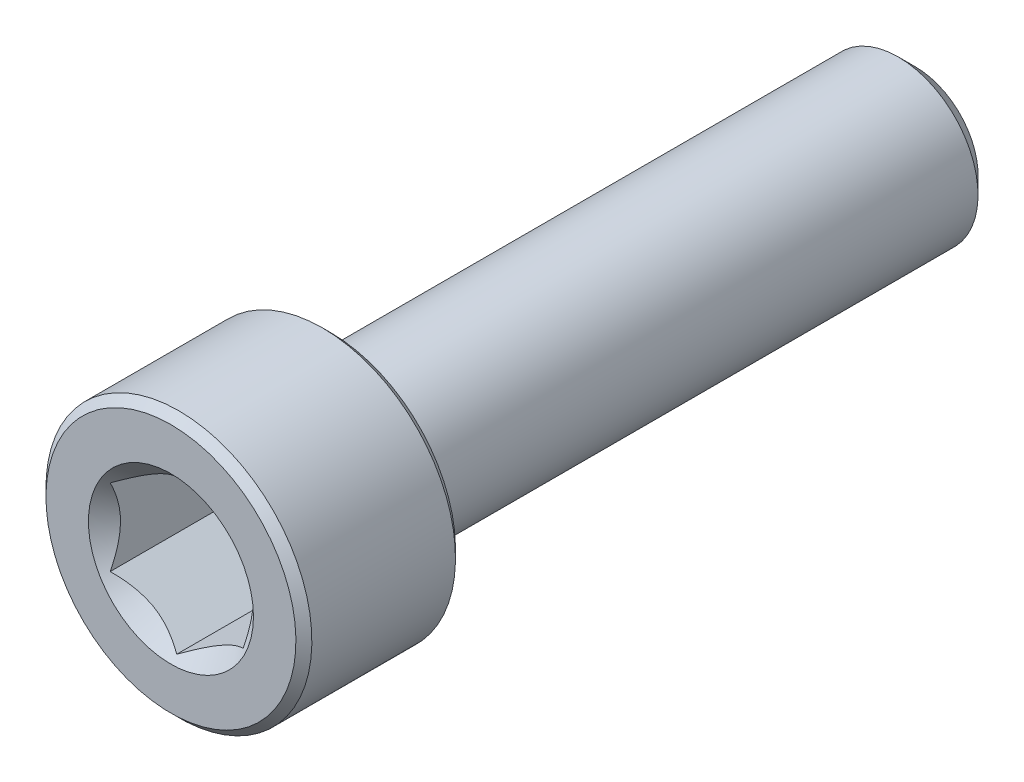
SolidWorks part; units mm, degrees
ref_plane "Front Plane" through (0, 0, 0) normal (0, 0, 1) x (1, 0, 0)
ref_plane "Top Plane" through (0, 0, 0) normal (0, 1, 0) x (1, 0, 0)
ref_plane "Right Plane" through (0, 0, 0) normal (1, 0, 0) x (0, 0, -1)
sketch "Sketch1" plane through (0, 0, 0) normal (1, 0, 0) x (0, 0, -1)
  line L0 (-14, 0) -> (14, 0) construction
  line L1 (14, 0) -> (14, 2.3505) construction
  line L2 (14, 2.3505) -> (13.3505, 3) construction
  line L3 (13.3505, 3) -> (13.25, 3) construction
  line L4 (13.25, 3) -> (-8, 3) construction
  line L5 (-8, 3) -> (-8, 5) construction
  line L6 (-8, 5) -> (-14, 5) construction
  line L7 (-14, 5) -> (-14, 0) construction
  line L8 (14, 2.3505) -> (14, 3) construction
  line L9 (13.9375, 3.1083) -> (14.4375, 2.2422) construction
  line L10 (14.4375, 2.2422) -> (14.9375, 3.1083) construction
  line L11 (14.9375, 3.1083) -> (13.9375, 3.1083) construction
  line L12 (14.4375, 3.1083) -> (14.4375, 3) construction
  line L13 (14.4375, 2.2422) -> (14.4375, 2.3505) construction
  line L14 (14.375, 2.3505) -> (14.5, 2.3505) construction
  line L15 (14, 3) -> (14.875, 3) construction
  line L16 (13.9688, 3.0541) -> (14.9062, 3.0541) construction
  line L17 (14, 0) -> (14, -3) construction
  line L18 (-8.3, 5) -> (-8, 4.7) construction
  line L19 (-13.7, 5) -> (-14, 4.7) construction
  line L20 (-8, 3) -> (-8, 0) construction
  line L21 (-8, 1.5) -> (-0.6667, 1.5) construction
  line L22 (-0.6667, 1.5) -> (6.6667, 1.5) construction
  line L23 (6.6667, 1.5) -> (14, 1.5) construction
  line L24 (-0.6667, 1.5) -> (-0.6667, 3) construction
  line L25 (-0.6667, 3) -> (-0.6667, 5) construction
  line L26 (6.6667, 1.5) -> (6.6667, 5) construction
  point P0 (-14, 2.5)
  point P3 (11.5, 3)
  point P4 (0, 0)
  point P18 (6.6667, 3)
  point P22 (14.4375, 2.3505)
  point P24 (13.25, 3)
  point P25 (14.4375, 3)
  point P28 (14.4375, 3.0541)
  point P29 (11.5, -3)
  point P30 (-0.6667, 3)
  point P31 (-11, 5)
  point P37 (-9.05, 5)
  point P38 (-13.55, 5)
  point P45 (-0.6667, 1.5)
  point P46 (6.6667, 1.5)
  dimension "D2" = 0.125
  dimension "D7" = 0.3
  dimension "D8" = 0.3
  dimension "D9" = 0.3
  dimension "D10" = 0.15
  dimension "D11" = 0.75
  dimension "Drive Size" = 5
  dimension "Head Diameter" = 10
  dimension "Head Height" = 6
  dimension "Thread Pitch" = 1
  dimension "Thread Dia" = 6
  dimension "Length" = 22
  dimension "D12" = 0.75
  dimension "D4" = 2.5
  dimension "D3" = 45
sketch "Sketch2" plane through (0, 0, 0) normal (1, 0, 0) x (0, 0, -1)
  line L0 (-14, 0) -> (-14, 4.7)
  line L1 (-13.7, 5) -> (-8.3, 5)
  line L2 (-8, 4.7) -> (-8, 3.3)
  line L4 (13.3505, 3) -> (14, 2.3505)
  line L5 (14, 2.3505) -> (14, 0)
  line L6 (-8, 5) -> (-14, 5) construction
  line L7 (14, 0) -> (-14, 0)
  line L8 (-13.7, 5) -> (-14, 4.7) construction
  line L10 (-13.7, 5) -> (-14, 4.7)
  line L14 (-8.3, 5) -> (-8, 4.7) construction
  line L16 (-8.3, 5) -> (-8, 4.7)
  line L17 (-8, 3) -> (-8, 5) construction
  line L19 (-7.7, 3) -> (13.3505, 3)
  line L20 (13.25, 3) -> (-8, 3) construction
  arc A1 (-8, 3.3) -> (-7.7, 3) centre (-7.7, 3.3) ccw
  dimension "D3" = 0.3
revolve "Revolve1" add sketch "Sketch2" angle 360 about L7
sketch "Sketch3" plane through (0, 0, 14) normal (0, 0, 1) x (1, 0, 0)
  line L1 (2.5, -1.4434) -> (2.5, 1.4434)
  line L2 (2.5, 1.4434) -> (0, 2.8868)
  line L3 (0, 2.8868) -> (-2.5, 1.4434)
  line L4 (-2.5, 1.4434) -> (-2.5, -1.4434)
  line L5 (-2.5, -1.4434) -> (0, -2.8868)
  line L6 (0, -2.8868) -> (2.5, -1.4434)
  circle A0 centre (0, 0) radius 2.5 construction
  circle A1 centre (0, 0) radius 5 construction
  circle A2 centre (0, 0) radius 5 construction
  circle A3 centre (0, 0) radius 2.8868 construction
  point P13 (0, 0)
  dimension "D1" = 5.7735
extrude "Cut-Extrude1" cut sketch "Sketch3" against normal offset from surface (5 mm away) 1 up to face at (0, 4.7, 8)
sketch "Sketch4" plane through (0, 0, 14) normal (0, 0, 1) x (1, 0, 0)
  circle A0 centre (0, 0) radius 3.1033
  dimension "D1" = 6.2065
extrude "Cut-Extrude2" cut sketch "Sketch4" against normal up to vertex (3 mm away) draft 45 up to point (0, 5, 11)
sketch "Sketch11" plane through (0, 0, 0) normal (1, 0, 0) x (0, 0, -1)
  line L0 (-14, 0) -> (14, 0) construction
  line L1 (-14, 0) -> (14, 0) construction
  line L2 (-3.875, 0) -> (-3.875, 3) construction
  line L3 (13.25, 3) -> (-8, 3) construction
  line L4 (9.875, 0) -> (9.875, 3) construction
  line L6 (14, 2.3505) -> (14, 3) construction
  point P2 (-3.875, 0)
  point P3 (9.875, 0)
  dimension "D1" = 4.125
  dimension "D2" = 4.125
sketch "Sketch6" [suppressed] plane through (0, 0, -14) normal (0, 0, -1) x (-1, 0, 0)
  circle A0 centre (0, 0) radius 3
curve "Helix/Spiral1" [suppressed] pitch 1 height 23 turns 23
sketch "Sketch10" [suppressed] plane through (0, 0, 0) normal (1, 0, 0) x (0, 0, -1)
  line L0 (-7.7, -5) -> (-7.7, 5)
  line L5 (-14, 0) -> (14, 0) construction
  line L6 (-7.7, 3) -> (-7.7, -3) construction
  point P3 (-7.7, 0)
split "Split1" [suppressed] bodies to split 106
sketch "Sketch7" [suppressed] plane through (0, 0, 0) normal (1, 0, 0) x (0, 0, -1)
  line L0 (13.9688, 3.0541) -> (14.9062, 3.0541)
  line L1 (14.9062, 3.0541) -> (14.5, 2.3505)
  line L2 (14.5, 2.3505) -> (14.375, 2.3505)
  line L3 (14.375, 2.3505) -> (13.9688, 3.0541)
sweep "Cut-Sweep1" [suppressed] cut profiles "Sketch7" path "Helix/Spiral1"
sketch "Sketch8" [suppressed] plane through (0, 0, 0) normal (1, 0, 0) x (0, 0, -1)
  line L0 (-8, 0) -> (-8, 3)
  line L1 (-7.7, -3) -> (-7.7, 3) construction
  line L2 (-8, 3) -> (-7.7, 3)
  line L4 (-7.7, 3) -> (-5.9679, 0)
  line L5 (-5.9679, 0) -> (-8, 0)
  line L6 (13.25, 3) -> (-8, 3) construction
  line L7 (-14, 0) -> (14, 0) construction
  dimension "D1" = 60
revolve "Revolve2" [suppressed] add sketch "Sketch8" angle 360 about L5
equation "\"D2@Sketch1\" = \"Thread Pitch@Sketch1\" / 8"
equation "\"D4@Helix/Spiral1\" = \"Thread Pitch@Sketch1\""
equation "\"D7@Sketch1\" = \"Head Height@Sketch1\" * .05"
equation "\"D8@Sketch1\"=\"D7@Sketch1\""
equation "\"D9@Sketch1\"=\"D7@Sketch1\""
equation "\"D10@Sketch1\"=\"D7@Sketch1\"/2"
equation "\"D11@Sketch1\"=\"D10@Sketch1\"*5"
equation "\"D4@Sketch1\"=\"Thread Pitch@Sketch1\"*2.5"
equation "\"D12@Sketch1\"=\"Thread Pitch@Sketch1\"*.75"
equation "\"D3@Helix/Spiral1\"=\"Length@Sketch1\"+\"Thread Pitch@Sketch1\""
equation "\"D3@Sketch2\"=\"Thread Dia@Sketch1\"*0.05"
equation "\"D1@Sketch11\"=\"Length@Sketch1\"*0.1875"
equation "\"D2@Sketch11\"=\"D1@Sketch11\""
equation "\"D1@Sketch4\"=\"D1@Sketch3\"*1.075"
